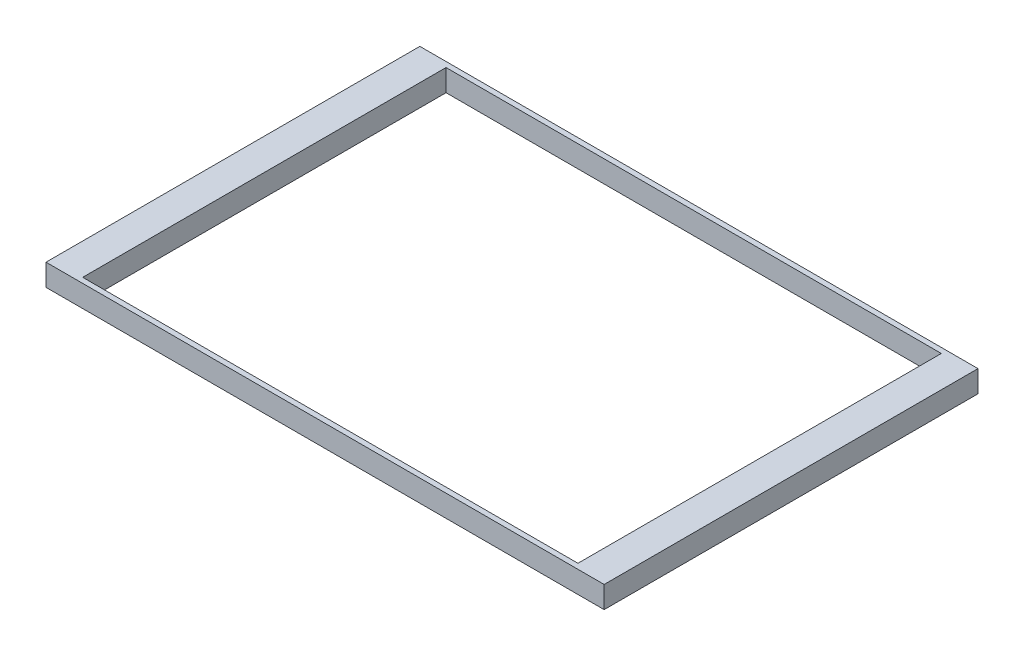
SolidWorks part; units mm, degrees
ref_plane "Front Plane" through (0, 0, 0) normal (0, 0, 1) x (1, 0, 0)
ref_plane "Top Plane" through (0, 0, 0) normal (0, 1, 0) x (1, 0, 0)
ref_plane "Right Plane" through (0, 0, 0) normal (1, 0, 0) x (0, 0, -1)
sketch "Sketch1" plane through (0, 0, 0) normal (0, 1, 0) x (1, 0, 0)
  line L1 (63.9, -42.8) -> (-63.9, -42.8)
  line L2 (63.9, -42.8) -> (63.9, 42.8)
  line L3 (63.9, 42.8) -> (-63.9, 42.8)
  line L4 (-63.9, -42.8) -> (-63.9, 42.8)
  line L5 (63.9, -42.8) -> (-63.9, 42.8) construction
  line L6 (63.9, 42.8) -> (-63.9, -42.8) construction
  point P0 (0, 0)
  dimension "D1" = 127.8
  dimension "D2" = 85.6
extrude "Boss-Extrude1" add sketch "Sketch1" along normal blind 5
ref_plane "Plane1" through (0, 5, 0) normal (0, 1, 0) x (1, 0, 0)
sketch "Sketch2" plane through (0, 5, 0) normal (0, 1, 0) x (1, 0, 0)
  line L1 (56.7, -41.6) -> (-56.7, -41.6)
  line L2 (56.7, -41.6) -> (56.7, 41.6)
  line L3 (56.7, 41.6) -> (-56.7, 41.6)
  line L4 (-56.7, -41.6) -> (-56.7, 41.6)
  line L5 (56.7, -41.6) -> (-56.7, 41.6) construction
  line L6 (56.7, 41.6) -> (-56.7, -41.6) construction
  point P0 (0, 0)
  dimension "D1" = 83.2
  dimension "D2" = 113.4
extrude "Cut-Extrude1" cut sketch "Sketch2" against normal blind 5
